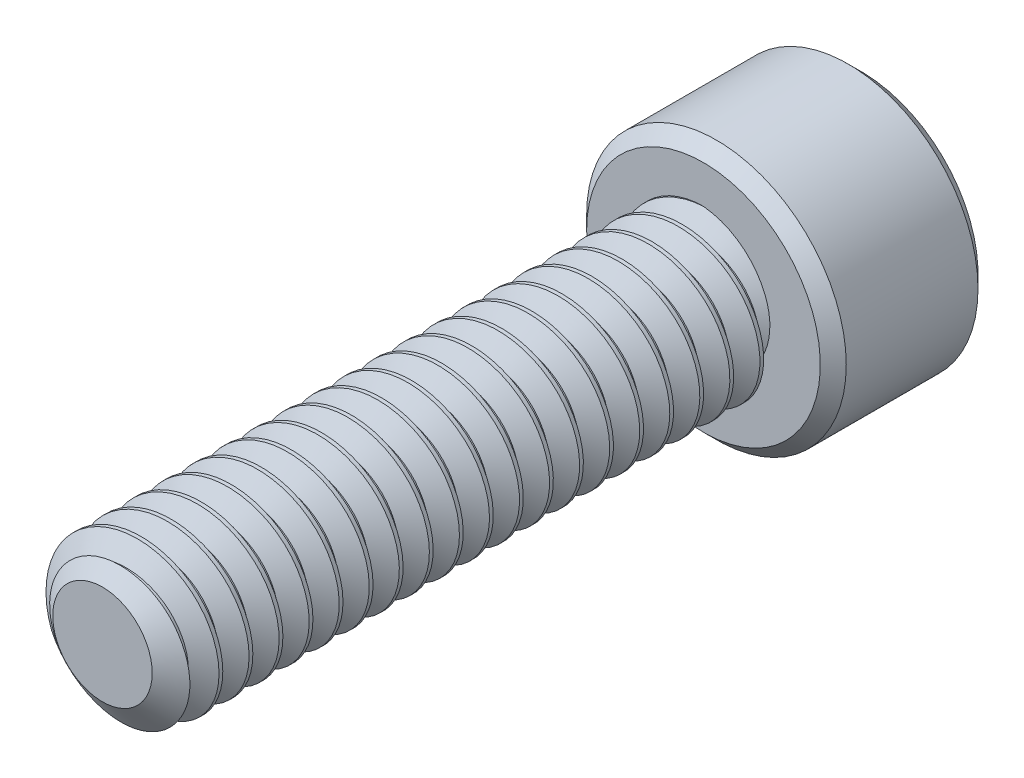
SolidWorks part; units mm, degrees
material "Cast Alloy Steel"
ref_plane "Front Plane" through (0, 0, 0) normal (0, 0, 1) x (1, 0, 0)
ref_plane "Top Plane" through (0, 0, 0) normal (0, 1, 0) x (1, 0, 0)
ref_plane "Right Plane" through (0, 0, 0) normal (1, 0, 0) x (0, 0, -1)
sketch "Sketch1" plane through (0, 0, 0) normal (0, 0, 1) x (1, 0, 0)
  circle A0 centre (0, 0) radius 2.0828
  dimension "OD" = 4.1656
extrude "Extrude1" add sketch "Sketch1" against normal blind 15.875
sketch "Sketch2" plane through (0, 0, 0) normal (0, 0, 1) x (1, 0, 0)
  circle A0 centre (0, 0) radius 2.0828 construction
  circle A1 centre (0, 0) radius 2.0828
curve "Helix/Spiral1" pitch 0.7937 height 16.6687 turns 21 parameters "pitch"=0.7937
sketch "Sketch3" plane through (0, 0, 0) normal (1, 0, 0) x (0, 0, -1)
  line L0 (-0.6945, 2.0828) -> (-0.3969, 1.5672)
  line L1 (-0.3969, 1.5672) -> (-0.2977, 1.5672)
  line L2 (-0.2977, 1.5672) -> (0, 2.0828)
  line L3 (-0.6945, 2.0828) -> (0, 2.0828)
  line L4 (-0.3473, 2.0828) -> (-0.3473, 1.5672) construction
  line L5 (-0.5457, 1.825) -> (-0.1488, 1.825) construction
  line L6 (0, 2.0828) -> (0, -2.0828) construction
  dimension "D1" = 0.0992
  dimension "D2" = 0.3969
  dimension "D3" = 60
sweep "Cut-Sweep1" cut profiles "Sketch3" path "Helix/Spiral1"
sketch "Sketch4" plane through (0, 0, 0) normal (1, 0, 0) x (0, 0, -1)
  line L0 (0.5388, 2.0828) -> (0, 1.3132)
  line L1 (0, 1.3132) -> (0, 2.0828)
  line L2 (0.5388, 2.0828) -> (0, 2.0828)
  line L3 (-0.6945, 2.0828) -> (0, 2.0828) construction
  line L4 (0, 0) -> (7.0209, 0) construction
  dimension "D1" = 55
  dimension "D2" = 0.254
revolve "Cut-Revolve1" cut sketch "Sketch4" angle 360 about L4
sketch "Sketch5" plane through (0, 0, 0) normal (1, 0, 0) x (0, 0, -1)
  line L0 (15.875, -1.5805) -> (15.875, 1.4861) construction
  line L1 (15.875, 2.2098) -> (87.4327, 2.2098)
  line L2 (15.875, 2.2098) -> (15.875, 0)
  line L3 (15.875, 0) -> (87.3125, 0)
  line L4 (87.3125, 1.8796) -> (87.3125, 0)
  line L5 (87.4327, 2.2098) -> (87.3125, 1.8796)
  line L6 (0, 0) -> (9.9695, 0) construction
  point P3 (87.3125, 2.2098)
  point P10 (87.3125, 2.2098)
  dimension "D1" = 0.3302
  dimension "Thread min" = 87.3125
  dimension "D2" = 0.127
  dimension "D3" = 20
revolve "partially thread" [suppressed] add sketch "Sketch5" angle 360 about L6
sketch "Sketch6" plane through (0, 0, -15.875) normal (0, 0, -1) x (-1, 0, 0)
  circle A0 centre (0, 0) radius 3.429
  dimension "head dia" = 6.858
extrude "Extrude2" add sketch "Sketch6" along normal blind 4.1656
sketch "Sketch7" plane through (0, 0, -20.0406) normal (0, 0, -1) x (-1, 0, 0)
  line L1 (0, 2.0622) -> (-1.7859, 1.0311)
  line L2 (-1.7859, 1.0311) -> (-1.7859, -1.0311)
  line L3 (-1.7859, -1.0311) -> (0, -2.0622)
  line L4 (0, -2.0622) -> (1.7859, -1.0311)
  line L5 (1.7859, -1.0311) -> (1.7859, 1.0311)
  line L6 (1.7859, 1.0311) -> (0, 2.0622)
  circle A0 centre (0, 0) radius 1.7859 construction
  dimension "hex dia" = 3.5719
extrude "Cut-Extrude1" cut sketch "Sketch7" against normal blind 2.6789
sketch "Sketch8" plane through (0, 0, -20.0406) normal (0, 0, -1) x (-1, 0, 0)
  circle A0 centre (0, 0) radius 2.0622
extrude "Cut-Extrude2" cut sketch "Sketch8" against normal through all draft 45
chamfer "Chamfer1" distance 0.3429 angle 45 2 edges at (-3.429, 0, -20.0406) (-3.429, 0, -15.875)
sketch "Sketch9" plane through (0, 0, 0) normal (1, 0, 0) x (0, 0, -1)
  line L0 (0, 2.0828) -> (0, -2.0828) construction
  line L1 (4.3656, 2.0828) -> (4.3656, -2.0828) construction
  dimension "D1" = 4.3656
equation "\"D3@Helix/Spiral1\" = \"screw length@Extrude1\"+\"pitch@Helix/Spiral1\""
equation "\"D1@Sketch3\" = \"pitch@Helix/Spiral1\"*.125"
equation "\"D2@Sketch3\" = \"pitch@Helix/Spiral1\"*.5"
equation "\"D1@Cut-Extrude1\" = \"hex dia@Sketch7\"*.75"
equation "\"D1@Chamfer1\" = \"head dia@Sketch6\"*.05"
equation "\"D1@Sketch9\" = \"pitch@Helix/Spiral1\"*5.5"
